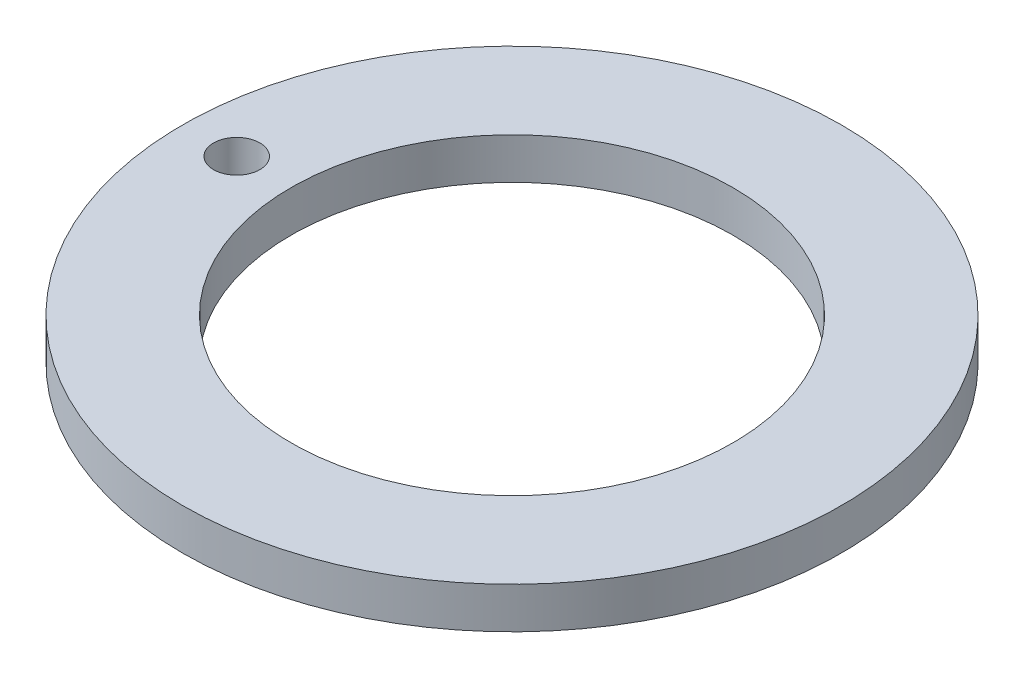
SolidWorks part; units mm, degrees
material "6061 Alloy"
ref_plane "Front Plane" through (0, 0, 0) normal (0, 0, 1) x (1, 0, 0)
ref_plane "Top Plane" through (0, 0, 0) normal (0, 1, 0) x (1, 0, 0)
ref_plane "Right Plane" through (0, 0, 0) normal (1, 0, 0) x (0, 0, -1)
sketch "Centering Ring Profile" plane through (0, 0, 0) normal (0, 1, 0) x (1, 0, 0)
  circle A0 centre (0, 0) radius 51.1048
  circle A1 centre (0, 0) radius 76.2
  dimension "D1" = 102.2096
  dimension "D2" = 152.4
extrude "Centering Ring Body" add sketch "Centering Ring Profile" along normal blind 9.525
sketch "Eye Bolt Hole Profile" plane through (0, 9.525, 0) normal (0, 1, 0) x (1, 0, 0)
  line L0 (-51.1048, 0) -> (-76.2, 0) construction
  circle A0 centre (0, 0) radius 51.1048 construction
  circle A1 centre (0, 0) radius 76.2 construction
  circle A2 centre (-63.6524, 0) radius 5.3581
  dimension "D1" = 10.7163
extrude "Eye Bolt Hole cut" cut sketch "Eye Bolt Hole Profile" against normal through all
equation "\"Ring Thickness\"= 0.375"
equation "\"Outer Diameter\"= 6"
equation "\"Inner Diameter\"= 4.024"
equation "\"D1@Centering Ring Profile\"=\"Inner Diameter\""
equation "\"D2@Centering Ring Profile\"=\"Outer Diameter\""
equation "\"D1@Centering Ring Body\"=\"Ring Thickness\""
